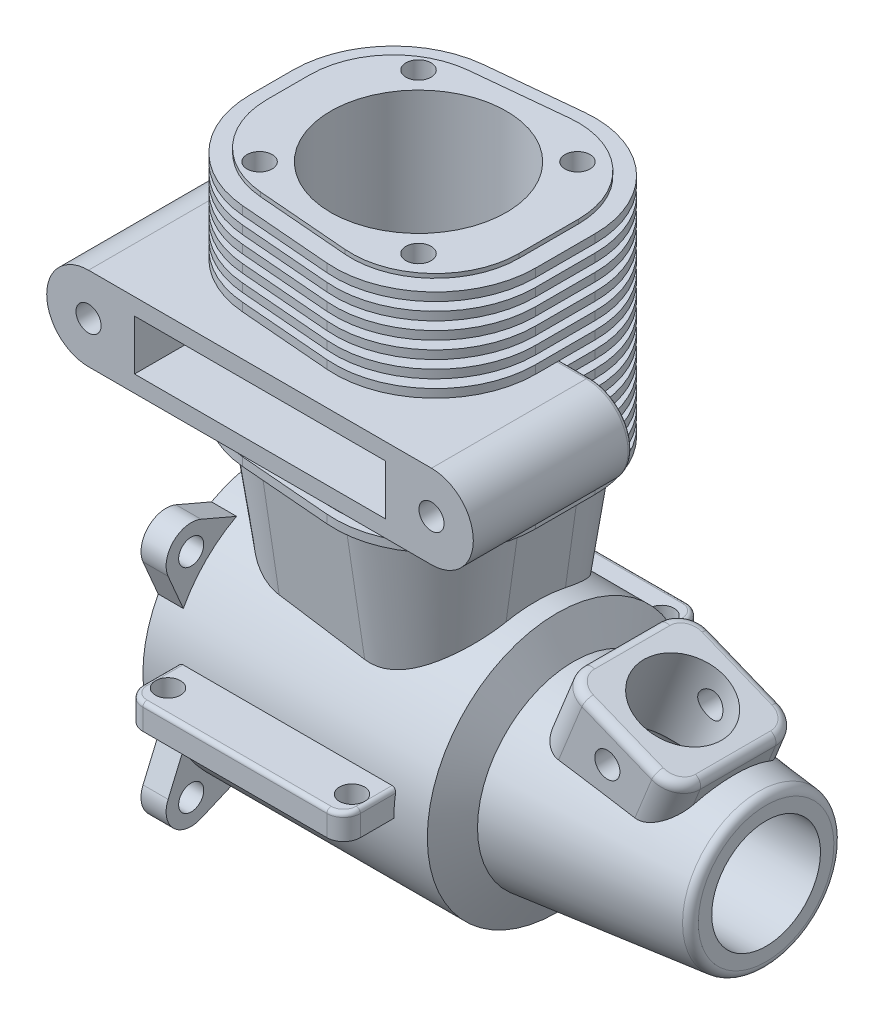
SolidWorks part; units mm, degrees
material "Alloy Steel"
ref_plane "Front Plane" through (0, 0, 0) normal (0, 0, 1) x (1, 0, 0)
ref_plane "Top Plane" through (0, 0, 0) normal (0, 1, 0) x (1, 0, 0)
ref_plane "Right Plane" through (0, 0, 0) normal (1, 0, 0) x (0, 0, -1)
sketch "Sketch1" plane through (0, 0, 0) normal (0, 0, 1) x (1, 0, 0)
  line L0 (29.5, 0) -> (-29.5, 0)
  line L1 (-29.5, 0) -> (-29.5, 15.5)
  line L2 (-29.5, 15.5) -> (4.5, 15.5)
  line L3 (4.5, 15.5) -> (6.5, 11.5)
  line L4 (6.5, 11.5) -> (29.5, 9)
  line L5 (29.5, 9) -> (29.5, 0)
  line L6 (-35, 0) -> (35, 0) construction
  point P4 (0, 0)
  dimension "D1" = 59
  dimension "D2" = 34
  dimension "D3" = 23
  dimension "D4" = 70
  dimension "D5" = 31
  dimension "D6" = 23
  dimension "D7" = 18
revolve "Revolve1" add sketch "Sketch1" angle 360 about L6
ref_plane "Plane1" through (0, 26, 0) normal (0, 1, 0) x (1, 0, 0)
sketch "Sketch2" plane through (0, 26, 0) normal (0, 1, 0) x (1, 0, 0)
  line L0 (-29.5, 0) -> (-29.5, 2.4483)
  line L2 (-29.5, 15.5) -> (-29.5, -15.5) construction
  line L3 (-18.6952, 14.3886) -> (-7.6952, 15.4897)
  line L4 (5.5, 3.5493) -> (5.5, -3.5493)
  line L5 (-7.4766, -15.5095) -> (-18.4766, -14.6114)
  line L6 (-29.5, -2.6512) -> (-29.5, 0)
  line L8 (-29.5, 0) -> (5.5, 0) construction
  arc A0 (-29.5, 2.4483) -> (-18.6952, 14.3886) centre (-17.5, 2.4483) cw
  arc A1 (-18.4766, -14.6114) -> (-29.5, -2.6512) centre (-17.5, -2.6512) cw
  arc A2 (-7.6952, 15.4897) -> (5.5, 3.5493) centre (-6.5, 3.5493) cw
  arc A3 (-7.6952, -15.4897) -> (5.5, -3.5493) centre (-6.5, -3.5493) ccw
  dimension "D1" = 12
  dimension "D2" = 12
  dimension "D4" = 35
  dimension "D7" = 12
  dimension "D3" = 31
  dimension "D5" = 29
  dimension "D6" = 11
extrude "Boss-Extrude1" add sketch "Sketch2" along normal blind 28 separate body contours L0 L8 L4 A2 L3 A0 | L8 L6 A1 L5 A3 L4 region at (-11.7156, 26, 6.9189) region at (-11.649, 26, -6.8769)
sketch "Sketch3" plane through (0, 54, 0) normal (0, 1, 0) x (1, 0, 0)
  line L0 (-27.5, 2.4483) -> (-27.5, -2.6512)
  line L1 (-18.3138, -12.618) -> (-7.3138, -13.5162)
  line L2 (3.5, -3.5493) -> (3.5, 3.5493)
  line L3 (-7.496, 13.4996) -> (-18.496, 12.3986)
  line L4 (-29.5, 2.4483) -> (-29.5, -2.6512)
  line L5 (-18.4766, -14.6114) -> (-7.4766, -15.5095)
  line L6 (5.5, -3.5493) -> (5.5, 3.5493)
  line L7 (-7.6952, 15.4897) -> (-18.6952, 14.3886)
  line L8 (-29.5, 2.4483) -> (-29.5, -2.6512)
  line L9 (-18.4766, -14.6114) -> (-7.4766, -15.5095)
  line L10 (5.5, -3.5493) -> (5.5, 3.5493)
  line L11 (-7.6952, 15.4897) -> (-18.6952, 14.3886)
  arc A0 (-27.5, -2.6512) -> (-18.3138, -12.618) centre (-17.5, -2.6512) ccw
  arc A1 (-7.3138, -13.5162) -> (3.5, -3.5493) centre (-6.5, -3.5493) ccw
  arc A2 (3.5, 3.5493) -> (-7.496, 13.4996) centre (-6.5, 3.5493) ccw
  arc A3 (-18.496, 12.3986) -> (-27.5, 2.4483) centre (-17.5, 2.4483) ccw
  arc A4 (-29.5, -2.6512) -> (-18.4766, -14.6114) centre (-17.5, -2.6512) ccw
  arc A5 (-7.4766, -15.5095) -> (5.5, -3.5493) centre (-6.5, -3.5493) ccw
  arc A6 (5.5, 3.5493) -> (-7.6952, 15.4897) centre (-6.5, 3.5493) ccw
  arc A7 (-18.6952, 14.3886) -> (-29.5, 2.4483) centre (-17.5, 2.4483) ccw
  arc A8 (-29.5, -2.6512) -> (-18.4766, -14.6114) centre (-17.5, -2.6512) ccw
  arc A9 (-7.4766, -15.5095) -> (5.5, -3.5493) centre (-6.5, -3.5493) ccw
  arc A10 (5.5, 3.5493) -> (-7.6952, 15.4897) centre (-6.5, 3.5493) ccw
  arc A11 (-18.6952, 14.3886) -> (-29.5, 2.4483) centre (-17.5, 2.4483) ccw
  dimension "D1" = 0
  dimension "D2" = 2
extrude "Cut-Extrude1" cut sketch "Sketch3" against normal blind 0.5
ref_plane "Plane2" through (0, 52.5, 0) normal (0, 1, 0) x (1, 0, 0)
sketch "Sketch4" plane through (0, 52.5, 0) normal (0, 1, 0) x (1, 0, 0)
  line L4 (-29.5, 2.4483) -> (-29.5, -2.6512)
  line L5 (-18.4766, -14.6114) -> (-7.4766, -15.5095)
  line L6 (5.5, -3.5493) -> (5.5, 3.5493)
  line L7 (-7.6952, 15.4897) -> (-18.6952, 14.3886)
  line L8 (-29.5, 2.4483) -> (-29.5, -2.6512)
  line L9 (-18.4766, -14.6114) -> (-7.4766, -15.5095)
  line L10 (5.5, -3.5493) -> (5.5, 3.5493)
  line L11 (-7.6952, 15.4897) -> (-18.6952, 14.3886)
  line L12 (-7.496, 13.4996) -> (-18.496, 12.3986)
  line L13 (-27.5, 2.4483) -> (-27.5, -2.6512)
  line L14 (-18.3138, -12.618) -> (-7.3138, -13.5162)
  line L15 (3.5, -3.5493) -> (3.5, 3.5493)
  line L16 (-7.496, 13.4996) -> (-18.496, 12.3986)
  line L17 (-27.5, 2.4483) -> (-27.5, -2.6512)
  line L18 (-18.3138, -12.618) -> (-7.3138, -13.5162)
  line L19 (3.5, -3.5493) -> (3.5, 3.5493)
  arc A4 (-18.6952, 14.3886) -> (-29.5, 2.4483) centre (-17.5, 2.4483) ccw
  arc A5 (-29.5, -2.6512) -> (-18.4766, -14.6114) centre (-17.5, -2.6512) ccw
  arc A6 (-7.4766, -15.5095) -> (5.5, -3.5493) centre (-6.5, -3.5493) ccw
  arc A7 (5.5, 3.5493) -> (-7.6952, 15.4897) centre (-6.5, 3.5493) ccw
  arc A8 (-18.6952, 14.3886) -> (-29.5, 2.4483) centre (-17.5, 2.4483) ccw
  arc A9 (-29.5, -2.6512) -> (-18.4766, -14.6114) centre (-17.5, -2.6512) ccw
  arc A10 (-7.4766, -15.5095) -> (5.5, -3.5493) centre (-6.5, -3.5493) ccw
  arc A11 (5.5, 3.5493) -> (-7.6952, 15.4897) centre (-6.5, 3.5493) ccw
  arc A12 (-18.496, 12.3986) -> (-27.5, 2.4483) centre (-17.5, 2.4483) ccw
  arc A13 (-27.5, -2.6512) -> (-18.3138, -12.618) centre (-17.5, -2.6512) ccw
  arc A14 (-7.3138, -13.5162) -> (3.5, -3.5493) centre (-6.5, -3.5493) ccw
  arc A15 (3.5, 3.5493) -> (-7.496, 13.4996) centre (-6.5, 3.5493) ccw
  arc A16 (-18.496, 12.3986) -> (-27.5, 2.4483) centre (-17.5, 2.4483) ccw
  arc A17 (-27.5, -2.6512) -> (-18.3138, -12.618) centre (-17.5, -2.6512) ccw
  arc A18 (-7.3138, -13.5162) -> (3.5, -3.5493) centre (-6.5, -3.5493) ccw
  arc A19 (3.5, 3.5493) -> (-7.496, 13.4996) centre (-6.5, 3.5493) ccw
  dimension "D1" = 0
  dimension "D2" = 0
extrude "Cut-Extrude2" cut sketch "Sketch4" against normal blind 1
pattern_linear "LPattern1" count 14 spacing 2 along (0, -1, 0) of "Cut-Extrude2"
sketch "Sketch5" plane through (0, 26, 0) normal (0, -1, 0) x (1, 0, 0)
  line L4 (3.5, -3.5493) -> (3.5, 3.5493)
  line L5 (-7.3138, 13.5162) -> (-18.3138, 12.618)
  line L6 (-27.5, 2.6512) -> (-27.5, -2.4483)
  line L7 (-18.496, -12.3986) -> (-7.496, -13.4996)
  line L8 (3.5, -3.5493) -> (3.5, 3.5493)
  line L9 (-7.3138, 13.5162) -> (-18.3138, 12.618)
  line L10 (-27.5, 2.6512) -> (-27.5, -2.4483)
  line L11 (-18.496, -12.3986) -> (-7.496, -13.4996)
  arc A4 (-7.496, -13.4996) -> (3.5, -3.5493) centre (-6.5, -3.5493) ccw
  arc A5 (3.5, 3.5493) -> (-7.3138, 13.5162) centre (-6.5, 3.5493) ccw
  arc A6 (-18.3138, 12.618) -> (-27.5, 2.6512) centre (-17.5, 2.6512) ccw
  arc A7 (-27.5, -2.4483) -> (-18.496, -12.3986) centre (-17.5, -2.4483) ccw
  arc A8 (-7.496, -13.4996) -> (3.5, -3.5493) centre (-6.5, -3.5493) ccw
  arc A9 (3.5, 3.5493) -> (-7.3138, 13.5162) centre (-6.5, 3.5493) ccw
  arc A10 (-18.3138, 12.618) -> (-27.5, 2.6512) centre (-17.5, 2.6512) ccw
  arc A11 (-27.5, -2.4483) -> (-18.496, -12.3986) centre (-17.5, -2.4483) ccw
  dimension "D1" = 0
extrude "Boss-Extrude2" add sketch "Sketch5" along normal blind 20 draft 8
sketch "Sketch6" plane through (29.5, 0, 0) normal (1, 0, 0) x (0, 0, -1)
  circle A0 centre (0, 0) radius 14
  dimension "D1" = 28
extrude "Cut-Extrude3" cut sketch "Sketch6" against normal up to next from offset 30 offset against normal yes
sketch "Sketch7" plane through (0, 54, 0) normal (0, 1, 0) x (1, 0, 0)
  line L0 (-27.5, -0.1014) -> (3.5, 0) construction
  line L1 (-27.5, 2.4483) -> (-27.5, -2.6512) construction
  line L2 (3.5, -3.5493) -> (3.5, 3.5493) construction
  circle A0 centre (-12, -0.0507) radius 10.5
  dimension "D1" = 21
extrude "Cut-Extrude4" cut sketch "Sketch7" against normal up to next
sketch "Sketch8" plane through (0, 0, 0) normal (0, 0, 1) x (1, 0, 0)
  line L0 (-1.5, 54) -> (-22.5, 54) construction
  line L1 (-1.5, 54) -> (-22.5, 54) construction
  line L2 (-12, 54) -> (-12, -42.9871) construction
  line L3 (19.5238, 14.0216) -> (-1.8593, -38.9035) construction
  line L4 (29.5, 9) -> (6.5, 11.5) construction
  line L5 (29.5, 9) -> (6.5, 11.5) construction
  line L6 (12.57, 16.8312) -> (26.4777, 11.2121)
  line L7 (26.4777, 11.2121) -> (23.256, 3.238)
  line L8 (23.256, 3.238) -> (8.4145, 6.546)
  line L9 (8.4145, 6.546) -> (12.57, 16.8312)
  point P8 (18, 10.25)
  point P13 (19.5238, 14.0216)
  dimension "D1" = 22
  dimension "D2" = 33
  dimension "D3" = 15
  dimension "D4" = 14.8415
extrude "Boss-Extrude3" add sketch "Sketch8" along normal mid plane 15
sketch "Sketch9" plane through (29.5, 0, 0) normal (1, 0, 0) x (0, 0, -1)
  circle A0 centre (0, 0) radius 6.5
  dimension "D1" = 13
extrude "Cut-Extrude5" cut sketch "Sketch9" against normal up to next
sketch "Sketch10" plane through (7.6099, 18.8352, 0) normal (0.3746, 0.9272, 0) x (0.9272, -0.3746, 0)
  line L0 (-32.45, 0) -> (32.45, 0) construction
  line L1 (5.3496, -7.5) -> (5.3496, 7.5) construction
  circle A0 centre (12.8496, 0) radius 5
  dimension "D1" = 10
  dimension "D2" = 7.5
extrude "Cut-Extrude6" cut sketch "Sketch10" against normal up to next
sketch "Sketch11" plane through (0, 0, -7.5) normal (0, 0, -1) x (-1, 0, 0)
  line L0 (-19.5238, 14.0216) -> (-7.9677, -14.5807) construction
  line L1 (-26.4777, 11.2121) -> (-12.57, 16.8312) construction
  line L2 (0, 17.1043) -> (0, -17.1043) construction
  circle A0 centre (-18.0254, 10.3129) radius 1.5
  dimension "D2" = 3
  dimension "D3" = 4
  dimension "D1" = 22
extrude "Cut-Extrude7" cut sketch "Sketch11" against normal blind 15 contours A0
sketch "Sketch12" plane through (-29.5, 0, 0) normal (-1, 0, 0) x (0, 0, 1)
  line L0 (0, 0) -> (12.7279, 12.7279) construction
  line L1 (17.1043, 0) -> (-17.1043, 0) construction
  line L2 (11.5472, 15.4858) -> (7.3061, 13.6701)
  line L3 (15.4858, 11.5472) -> (13.6701, 7.3061)
  circle A0 centre (12.7279, 12.7279) radius 1.5
  arc A1 (15.4858, 11.5472) -> (11.5472, 15.4858) centre (12.7279, 12.7279) ccw
  arc A2 (10.5648, 11.3418) -> (2.6512, 15.2716) centre (0, 0) ccw construction
  arc A3 (7.3061, 13.6701) -> (13.6701, 7.3061) centre (0, 0) cw
  dimension "D3" = 3
  dimension "D4" = 6
  dimension "D6" = 15.5
  dimension "D1" = 45
  dimension "D2" = 18
  dimension "D5" = 9
extrude "Boss-Extrude4" add sketch "Sketch12" against normal blind 3
pattern_circular "CirPattern1" count 4 over 360 about axis through (-29.5, 0, 0) along (-1, 0, 0) of "Boss-Extrude4"
sketch "Sketch13" plane through (0, 0, 0) normal (0, 1, 0) x (1, 0, 0)
  line L0 (-32.45, 0) -> (32.45, 0) construction
  line L1 (-25.5, 21.5) -> (0.5, 21.5)
  line L2 (-25.5, 21.5) -> (-25.5, 11.5)
  line L3 (-25.5, 11.5) -> (0.5, 11.5)
  line L4 (0.5, 21.5) -> (0.5, 11.5)
  line L5 (4.5, 15.5) -> (-29.5, 15.5) construction
  line L6 (4.5, 15.5) -> (-29.5, 15.5) construction
  line L7 (-12.5, 15.5) -> (-12.5, 21.5) construction
  circle A0 centre (-23.5, 18.5) radius 1.5
  circle A1 centre (-1.5, 18.5) radius 1.5
  dimension "D4" = 3
  dimension "D5" = 18.5
  dimension "D6" = 22
  dimension "D1" = 26
  dimension "D2" = 21.5
  dimension "D3" = 10
extrude "Boss-Extrude5" add sketch "Sketch13" along normal blind 3
sketch "Sketch14" plane through (-29.5, 0, 0) normal (-1, 0, 0) x (0, 0, 1)
  circle A0 centre (0, 0) radius 14 construction
  circle A1 centre (0, 0) radius 14
extrude "Cut-Extrude8" cut sketch "Sketch14" against normal up to surface (29 mm away) up to face at (-0.5, 6.5, 0)
mirror "Mirror2" about plane through (0, 0, 0) normal (0, 0, 1) of "Cut-Extrude8", "Boss-Extrude5"
sketch "Sketch15" plane through (0, 54, 0) normal (0, 1, 0) x (1, 0, 0)
  line L1 (-2.5, -9.5507) -> (-21.5, -9.5507) construction
  line L2 (-2.5, -9.5507) -> (-2.5, 9.4493) construction
  line L3 (-2.5, 9.4493) -> (-21.5, 9.4493) construction
  line L4 (-21.5, -9.5507) -> (-21.5, 9.4493) construction
  line L5 (-2.5, -9.5507) -> (-21.5, 9.4493) construction
  line L6 (-2.5, 9.4493) -> (-21.5, -9.5507) construction
  circle A0 centre (-21.5, 9.4493) radius 1.5
  circle A1 centre (-2.5, 9.4493) radius 1.5
  circle A2 centre (-2.5, -9.5507) radius 1.5
  circle A3 centre (-21.5, -9.5507) radius 1.5
  point P0 (-12, -0.0507)
  dimension "D3" = 3
  dimension "D1" = 19
  dimension "D2" = 19
extrude "Cut-Extrude9" cut sketch "Sketch15" against normal blind 17
ref_plane "Plane3" through (-12, 0, 0) normal (-1, 0, 0) x (0, 0, 1)
sketch "Sketch18" plane through (-12, 0, 0) normal (-1, 0, 0) x (0, 0, 1)
  line L0 (0, -32.45) -> (0, 32.45) construction
  line L1 (19, 32) -> (0, 32)
  line L2 (19, 32) -> (19, 42)
  line L3 (19, 42) -> (0, 42)
  line L4 (0, 32) -> (0, 42)
  line L5 (19, 32) -> (0, 42) construction
  line L6 (19, 42) -> (0, 32) construction
  line L7 (12.618, 54) -> (2.6512, 54) construction
  point P0 (9.5, 37)
  dimension "D1" = 19
  dimension "D2" = 10
  dimension "D3" = 17
extrude "Boss-Extrude6" add sketch "Sketch18" along normal mid plane 51
sketch "Sketch19" plane through (0, 0, 19) normal (0, 0, 1) x (1, 0, 0)
  line L2 (-32.5, 42) -> (-37.5, 42)
  line L3 (8.5, 32) -> (13.5, 32)
  line L6 (13.5, 32) -> (13.5, 42)
  line L7 (13.5, 42) -> (-37.5, 42)
  line L8 (-37.5, 42) -> (-37.5, 32)
  line L9 (-37.5, 32) -> (13.5, 32)
  line L10 (13.5, 32) -> (13.5, 42)
  line L11 (13.5, 42) -> (8.5, 42)
  line L12 (-37.5, 42) -> (-37.5, 32)
  line L13 (-37.5, 32) -> (-32.5, 32)
  arc A0 (-32.5, 32) -> (-32.5, 42) centre (-32.5, 37) cw
  arc A1 (8.5, 32) -> (8.5, 42) centre (8.5, 37) ccw
  circle A2 centre (-32.5, 37) radius 1.5
  circle A3 centre (8.5, 37) radius 1.5
  point P11 (-37.5, 37)
  line M5 (13.5, 32) -> (13.5, 42)
  line M6 (13.5, 42) -> (-37.5, 42)
  line M7 (-37.5, 42) -> (-37.5, 32)
  line M8 (-37.5, 32) -> (13.5, 32)
  dimension "D1" = 0
  dimension "D2" = 5
  dimension "D3" = 5
  dimension "D4" = 3
  dimension "D5" = 3
extrude "Cut-Extrude10" cut sketch "Sketch19" against normal up to next contours A1 L10 M6 | A1 M8 M5 | A0 M7 M6 | A0 L12 M8 | A2 | A3 region at (-36.3832, 40.8832, 19) region at (12.3832, 40.8832, 19) region at (-36.3832, 33.1168, 19) region at (12.3832, 33.1168, 19) region at (-32.5, 37, 19) region at (8.5, 37, 19)
sketch "Sketch20" plane through (0, 0, 19) normal (0, 0, 1) x (1, 0, 0)
  line L0 (-12, 17.3007) -> (-12, -17.3007) construction
  line L1 (3, 34) -> (-27, 34)
  line L2 (3, 34) -> (3, 40)
  line L3 (3, 40) -> (-27, 40)
  line L4 (-27, 34) -> (-27, 40)
  line L5 (3, 34) -> (-27, 40) construction
  line L6 (3, 40) -> (-27, 34) construction
  line L7 (-32.5, 42) -> (8.5, 42) construction
  point P0 (-12, 37)
  dimension "D1" = 30
  dimension "D2" = 6
  dimension "D3" = 5
extrude "Cut-Extrude11" cut sketch "Sketch20" against normal blind 19
sketch "Sketch21" plane through (0, 54, 0) normal (0, 1, 0) x (1, 0, 0)
  circle A0 centre (-12, -0.0507) radius 10.5 construction
  circle A1 centre (-12, -0.0507) radius 10.5
extrude "Cut-Extrude12" cut sketch "Sketch21" against normal blind 30
fillet "Fillet1" radius 2 4 edges at (0.5, 1.5, -21.5) (-25.5, 1.5, -21.5) (-25.5, 1.5, 21.5) (0.5, 1.5, 21.5)
fillet "Fillet2" radius 3 4 edges at (25.4105, 8.5706, 7.5) (10.8538, 12.5836, 7.5) (10.8538, 12.5836, -7.5) (25.4105, 8.5706, -7.5)
fillet "Fillet3" radius 1 9 edges at (26.4777, 11.2121, 0) (25.663, 11.5412, 6.6213) (19.5238, 14.0216, 7.5) (13.3847, 16.502, 6.6213) (12.57, 16.8312, 0) (13.3847, 16.502, -6.6213) (19.5238, 14.0216, -7.5) (25.663, 11.5412, -6.6213) (29.5, -9, 0)
fillet "Fillet4" radius 0.5 16 edges at (-30, 42, 0) (-30, 32, 0) (6, 32, 0) (13.5, 37, 0) (0.5, 3, 17.3535) (-0.0858, 3, 20.9142) (-25.5, 3, 17.3535) (-24.9142, 3, 20.9142) (0.5, 3, -17.3535) (-0.0858, 3, -20.9142) (-25.5, 3, -17.3535) (-24.9142, 3, -20.9142) (-37.5, 37, 0) (6, 42, 0) (-12.5, 3, 21.5) (-12.5, 3, -21.5)
